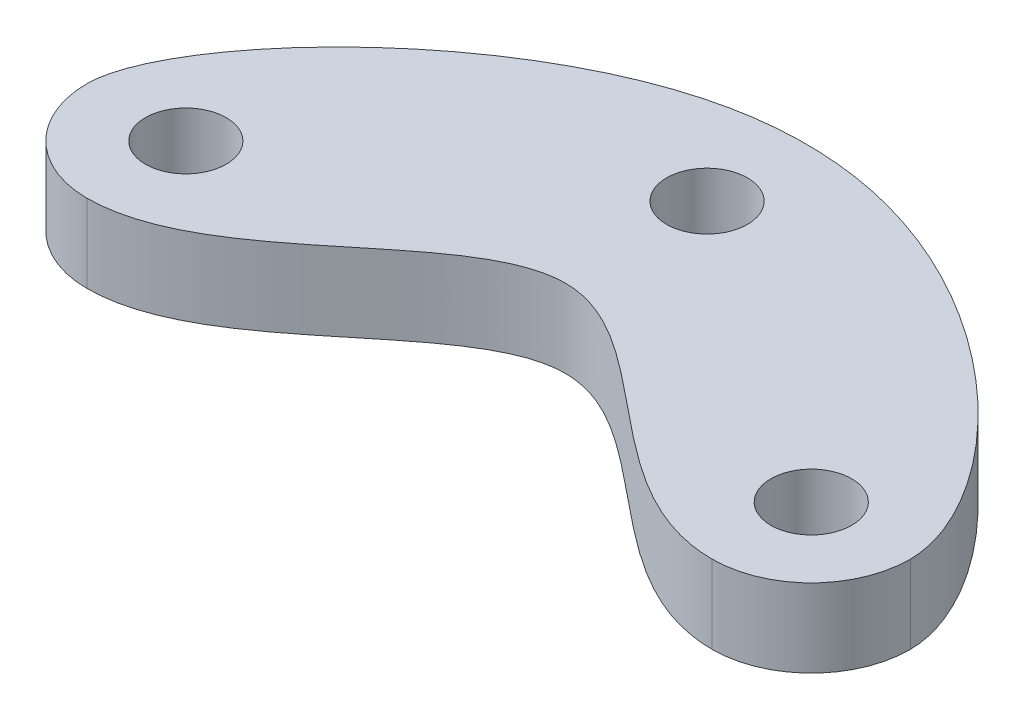
SolidWorks part; units mm, degrees
ref_plane "Front Plane" through (0, 0, 0) normal (0, 0, 1) x (1, 0, 0)
ref_plane "Top Plane" through (0, 0, 0) normal (0, 1, 0) x (1, 0, 0)
ref_plane "Right Plane" through (0, 0, 0) normal (1, 0, 0) x (0, 0, -1)
ref_axis "Axis1" through (-33.0333, 0, 0) along (1, 0, 0)
ref_axis "Axis2" through (0, 24.5224, 0) along (0, -1, 0)
ref_axis "Axis3" through (0, 0, -30.7663) along (0, 0, 1)
sketch "Sketch1" plane through (0, 0, 0) normal (0, 1, 0) x (1, 0, 0)
  line L0 (-24, 0) -> (24, 0) construction
  line L2 (0, 0) -> (0, 16) construction
  circle A3 centre (-24, 0) radius 3.1
  circle A4 centre (24, 0) radius 3.1
  circle A5 centre (0, 16) radius 3.1
  circle A6 centre (0, 16) radius 7.6 construction
  circle A7 centre (24, 0) radius 7.6 construction
  circle A8 centre (-24, 0) radius 7.6 construction
  arc A9 (-31.5999, 0.0357) -> (-24, -7.6) centre (-24, 0) ccw
  arc A10 (24, -7.6) -> (31.6, 0) centre (24, 0) ccw
  spline S0 degree 3 poles (-31.5999, 0.0357) (-31.5779, 6.454) (-15.874, 23.7758) (16.0196, 23.704) (31.5521, 7.1204) (31.6, 0) knots 0 0 0 0 0.447467 0.547467 1 1 1 1
  spline S1 degree 3 poles (-24, -7.6) (-14.6683, -7.615) (0.0112, 17.8222) (14.6459, -7.5661) (24, -7.6) knots 0 0 0 0 0.5 1 1 1 1
  point P3 (0, 0)
  point P23 (0, 0)
  dimension "D1" = 48
  dimension "D3" = 16
  dimension "D2" = 6.2
  dimension "D4" = 4.5
extrude "Boss-Extrude1" add sketch "Sketch1" along normal blind 6
